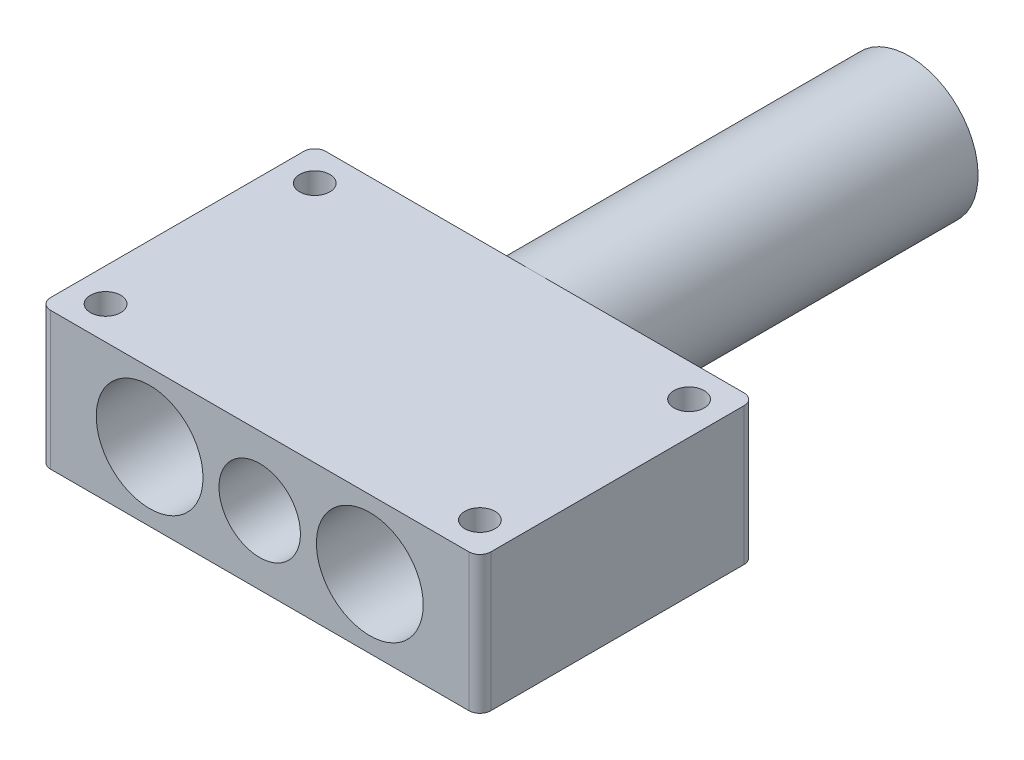
SolidWorks part; units mm, degrees
ref_plane "Front Plane" through (0, 0, 0) normal (0, 0, 1) x (1, 0, 0)
ref_plane "Top Plane" through (0, 0, 0) normal (0, 1, 0) x (1, 0, 0)
ref_plane "Right Plane" through (0, 0, 0) normal (1, 0, 0) x (0, 0, -1)
sketch "Sketch1" plane through (0, 0, 0) normal (0, 1, 0) x (1, 0, 0)
  line L1 (-40, 25) -> (40, 25)
  line L2 (-40, 25) -> (-40, -25)
  line L3 (-40, -25) -> (40, -25)
  line L4 (40, 25) -> (40, -25)
  line L5 (-40, 25) -> (40, -25) construction
  line L6 (-40, -25) -> (40, 25) construction
  point P0 (0, 0)
  dimension "D1" = 50
  dimension "D2" = 80
extrude "Boss-Extrude1" add sketch "Sketch1" along normal blind 25
hole_wizard "M5 Clearance Hole1" positions "Sketch2" profile "Sketch3" hole size "M5" standard "ANSI Metric" end condition through all
sketch "Sketch2" plane through (0, 25, 0) normal (0, 1, 0) x (1, 0, 0)
  line L0 (-34, 19) -> (-34, -19) construction
  line L1 (-34, -19) -> (34, -19) construction
  line L2 (34, -19) -> (34, 19) construction
  line L3 (34, 19) -> (-34, 19) construction
  line L5 (40, 25) -> (-40, 25) construction
  line L6 (-40, 25) -> (-40, -25) construction
  point P0 (-34, 19)
  point P2 (34, 19)
  point P4 (34, -19)
  point P6 (-34, -19)
  point P19 (0, 25)
  point P20 (0, 19)
  dimension "D1" = 6
  dimension "D2" = 6
  dimension "D3" = 38
sketch "Sketch3" plane through (-34, 25, -19) normal (1, 0, 0) x (0, 0, 1)
  line L0 (0, 0) -> (0, 25)
  line L1 (0, 25) -> (2.75, 25)
  line L2 (2.75, 25) -> (2.75, 0)
  line L5 (2.75, 0) -> (0, 0)
  line L11 (0, -6.35) -> (0, 107.95) construction
  dimension "Thru Hole Dia." = 5.5
  dimension "Thru Hole Depth" = 25
sketch "Sketch4" plane through (0, 0, 25) normal (0, 0, 1) x (1, 0, 0)
  line L0 (-40, 25) -> (-40, 0) construction
  line L1 (-20, 12.5) -> (0, 12.5) construction
  line L2 (0, 12.5) -> (20, 12.5) construction
  circle A0 centre (0, 12.5) radius 7.4
  circle A1 centre (-20, 12.5) radius 9.7
  circle A2 centre (20, 12.5) radius 9.7
  point P6 (-40, 12.5)
  dimension "D1" = 14.8
  dimension "D2" = 19.4
  dimension "D3" = 20
sketch "Sketch5" plane through (0, 0, -25) normal (0, 0, -1) x (-1, 0, 0)
  line L0 (-40, 25) -> (40, 25) construction
  line L1 (40, 25) -> (40, 0) construction
  circle A0 centre (0, 12.5) radius 12.5
  circle A1 centre (0, 12.5) radius 6.985
  point P9 (40, 12.5)
  dimension "D1" = 13.97
extrude "Boss-Extrude2" add sketch "Sketch5" along normal blind 68
extrude "Cut-Extrude2" cut sketch "Sketch4" against normal blind 29 contours A1 | A2 region at (-20, 12.5, 25) region at (20, 12.5, 25)
extrude "Cut-Extrude3" cut sketch "Sketch4<4>" against normal through all contours A0 region at (0, 12.5, 25)
sketch "Sketch4<4>" plane through (0, 0, 25) normal (0, 0, 1) x (1, 0, 0) same geometry as "Sketch4"
sketch "Sketch6" plane through (0, 0, -4) normal (0, 0, 1) x (1, 0, 0)
  circle A0 centre (-20, 12.5) radius 6.5
  circle A1 centre (20, 12.5) radius 6.5
  dimension "D1" = 13
extrude "Cut-Extrude4" cut sketch "Sketch6" against normal through all
ref_plane "Plane1" through (0, 0, -0.5) normal (0, 0, 1) x (1, 0, 0)
sketch "Sketch7" plane through (0, 0, -0.5) normal (0, 0, 1) x (1, 0, 0)
  circle A0 centre (-20, 12.5) radius 9.5
  circle A1 centre (-20, 12.5) radius 9.7
  circle A2 centre (20, 12.5) radius 9.7
  circle A3 centre (20, 12.5) radius 9.5
  dimension "D1" = 19
  dimension "D2" = 19.4
  dimension "D3" = 19.4
  dimension "D4" = 19
extrude "Boss-Extrude3" add sketch "Sketch7" along normal blind 1.3
chamfer "Chamfer2" distance 0.2 angle 45 4 edges at (29.5, 12.5, -0.5) (29.5, 12.5, 0.8) (-10.5, 12.5, -0.5) (-10.5, 12.5, 0.8)
hole_wizard "Hole2" positions "Sketch8" profile "Sketch9" legacy
sketch "Sketch8" plane through (0, 0, 0) normal (0, -1, 0) x (-1, 0, 0)
  point P0 (-9, 0)
  point P4 (9, 0)
  dimension "D1" = 9
  dimension "D2" = 9
sketch "Sketch9" plane through (9, 0, 0) normal (1, 0, 0) x (0, 0, -1)
  line L0 (0, 0) -> (0, 6)
  line L1 (0, 6) -> (2.4, 6)
  line L2 (2.4, 6) -> (2.4, 4)
  line L3 (2.4, 4) -> (2.7, 4)
  line L4 (2.7, 4) -> (2.7, 0)
  line L5 (2.7, 0) -> (0, 0)
  line L6 (0, 110) -> (0, -10) construction
  dimension "Diameter" = 4.8
  dimension "Depth" = 6
  dimension "C-Bore Diameter" = 5.4
  dimension "C-Bore Depth" = 4
chamfer "Chamfer3" distance 4 distance2 0.3 2 edges at (-9, 4, -2.7) (9, 4, -2.7) first distance on face at (-9, 4, -2.7) first distance on face at (9, 4, -2.7)
fillet "Fillet1" radius 2 4 edges at (40, 12.5, -25) (40, 12.5, 25) (-40, 12.5, -25) (-40, 12.5, 25)
